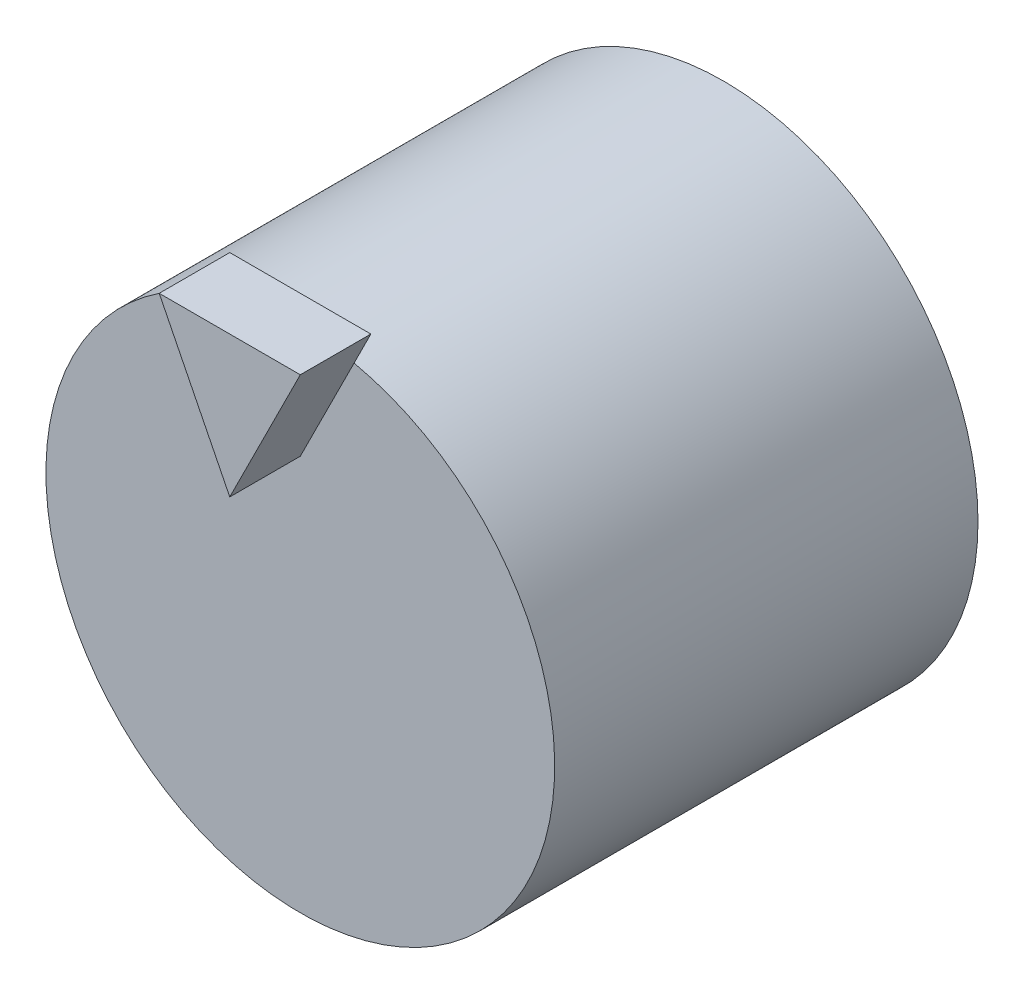
SolidWorks part; units mm, degrees
ref_plane "Front Plane" through (0, 0, 0) normal (0, 0, 1) x (1, 0, 0)
ref_plane "Top Plane" through (0, 0, 0) normal (0, 1, 0) x (1, 0, 0)
ref_plane "Right Plane" through (0, 0, 0) normal (1, 0, 0) x (0, 0, -1)
other "Configuration Table"
sketch "Sketch1" plane through (0, 0, 0) normal (0, 0, 1) x (1, 0, 0)
  circle A0 centre (0, 0) radius 36.0555
extrude "Boss-Extrude1" add sketch "Sketch1" along normal blind 60
sketch "Sketch3" plane through (0, 0, 60) normal (0, 0, 1) x (1, 0, 0)
  line L0 (-10, 40) -> (0, 20)
  line L1 (0, 20) -> (10, 40)
  line L2 (-10, 40) -> (10, 40)
ref_axis "Axis1" through (0, 0, 60) along (0, 0, -1)
extrude "Boss-Extrude2" add sketch "Sketch3" along normal blind 10
